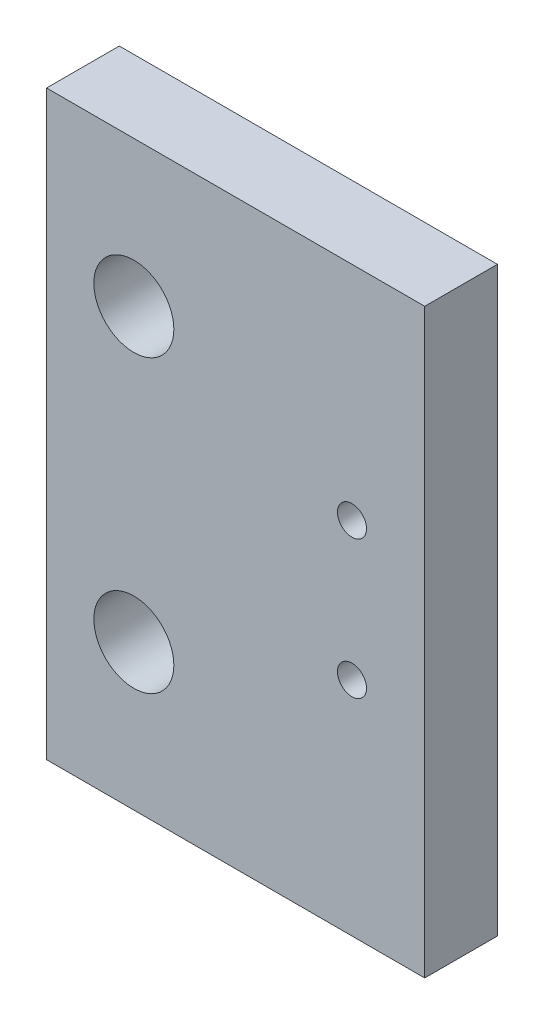
SolidWorks part; units mm, degrees
ref_plane "Plan de face" through (0, 0, 0) normal (0, 0, 1) x (1, 0, 0)
ref_plane "Plan de dessus" through (0, 0, 0) normal (0, 1, 0) x (1, 0, 0)
ref_plane "Plan de droite" through (0, 0, 0) normal (1, 0, 0) x (0, 0, -1)
sketch "Esquisse1" plane through (0, 0, 0) normal (0, 0, 1) x (1, 0, 0)
  line L0 (-38.6032, 13.3792) -> (-38.6032, -6.6208) construction
  line L1 (-44.6032, 23.3792) -> (-18.6032, 23.3792)
  line L2 (-44.6032, 23.3792) -> (-44.6032, -16.6208)
  line L3 (-44.6032, -16.6208) -> (-18.6032, -16.6208)
  line L4 (-18.6032, 23.3792) -> (-18.6032, -16.6208)
  line L5 (-23.6032, 8.1292) -> (-23.6032, -1.3708) construction
  circle A0 centre (-38.6032, 13.3792) radius 2.75
  circle A1 centre (-38.6032, -6.6208) radius 2.75
  circle A2 centre (-23.6032, 8.1292) radius 1
  circle A3 centre (-23.6032, -1.3708) radius 1
  point P8 (-38.6032, 3.3792)
  point P10 (-44.6032, 3.3792)
  point P15 (-23.6032, 3.3792)
  point P16 (-18.6032, 3.3792)
  point P17 (0, 0)
  dimension "D3" = 5.5
  dimension "D6" = 2
  dimension "D1" = 20
  dimension "D2" = 40
  dimension "D4" = 6
  dimension "D5" = 5
  dimension "D7" = 15
  dimension "D8" = 9.5
extrude "Boss.-Extru.1" add sketch "Esquisse1" along normal blind 5
